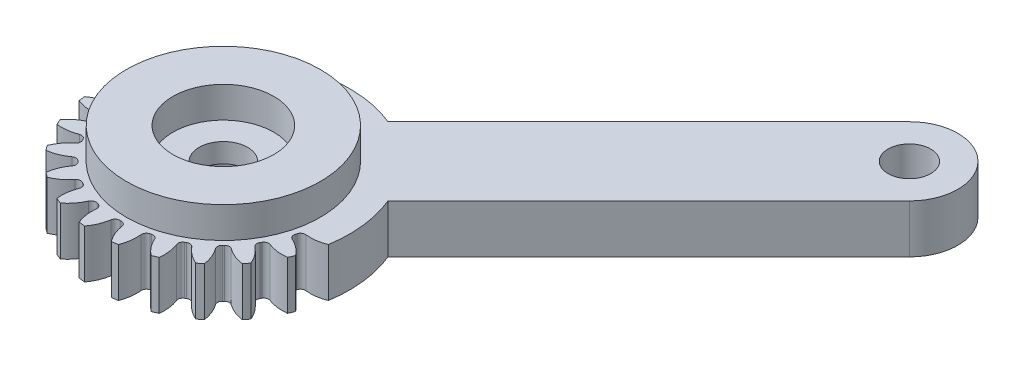
SolidWorks part; units mm, degrees
ref_plane "Front Plane" through (0, 0, 0) normal (0, 0, 1) x (1, 0, 0)
ref_plane "Top Plane" through (0, 0, 0) normal (0, 1, 0) x (1, 0, 0)
ref_plane "Right Plane" through (0, 0, 0) normal (1, 0, 0) x (0, 0, -1)
sketch "Sketch2" plane through (0, 0, 0) normal (0, 1, 0) x (1, 0, 0)
  circle A0 centre (0, 0) radius 13
  circle A1 centre (0, 0) radius 5.2
  dimension "D1" = 10.4
  dimension "D2" = 26
extrude "Boss-Extrude1" add sketch "Sketch2" along normal blind 5
sketch "Sketch3" plane through (0, 5, 0) normal (0, 1, 0) x (1, 0, 0)
  line L0 (0, 0) -> (0, 13) construction
  line L1 (-0.5275, 10.5869) -> (0, 0) construction
  line L2 (0, 9.6865) -> (14.5717, -30.349) construction
  arc A0 (0.5275, 10.5869) -> (-0.5275, 10.5869) centre (0, 0) ccw
  arc A1 (0.8347, 11.9709) -> (-0.8347, 11.9709) centre (0, 0) ccw construction
  arc A2 (1.3791, 12.9266) -> (-1.3791, 12.9266) centre (0, 0) ccw
  circle A3 centre (0, 0) radius 13 construction
  arc A5 (-1.3791, 12.9266) -> (-0.5275, 10.5869) centre (-4.7448, 10.3768) cw
  arc A6 (1.3791, 12.9266) -> (0.5275, 10.5869) centre (4.7448, 10.3768) ccw
  point P16 (-0.7769, 11.821)
  dimension "D1" = 24
  dimension "D2" = 2.4
  dimension "D3" = 20
  dimension "D4" = 1.6708
extrude "Cut-Extrude1" cut sketch "Sketch3" against normal through all
fillet "Fillet1" radius 0.5 2 edges at (0.5275, 2.5, -10.5869) (-0.5275, 2.5, -10.5869)
fillet "圆角1" [suppressed] radius 0.2
pattern_circular "CirPattern1" count 24 over 360 about axis through (0, 5, 0) along (0, -1, 0) of "Cut-Extrude1", "Fillet1", "圆角1" reverse direction yes
sketch "草图3" plane through (0, 5, 0) normal (0, 1, 0) x (1, 0, 0)
  circle A0 centre (0, 0) radius 12 construction
  dimension "D1" = 24
sketch "草图4" plane through (0, 5, 0) normal (0, 1, 0) x (1, 0, 0)
  line L0 (0, 0) -> (35.3553, 35.3553) construction
  line L1 (9.1924, 2.1213) -> (38.8909, 31.8198)
  line L2 (2.1213, 9.1924) -> (31.8198, 38.8909)
  line L3 (2.1213, 9.1924) -> (9.1924, 2.1213)
  line L5 (-5.2, 0) -> (5.2, 0) construction
  line L6 (-1.6968, 12.8888) -> (-1.2314, 9.3533)
  line L7 (9.3533, -1.2314) -> (12.8888, -1.6968)
  arc A0 (38.8909, 31.8198) -> (31.8198, 38.8909) centre (35.3553, 35.3553) ccw
  circle A1 centre (35.3553, 35.3553) radius 2.2
  circle A2 centre (0, 0) radius 5.2 construction
  arc A3 (4.9749, 12.0104) -> (-1.6968, 12.8888) centre (0, 0) ccw
  arc A4 (5.269, 11.8843) -> (4.6777, 12.1293) centre (0, 0) ccw construction
  arc A5 (-1.3791, 12.9266) -> (-2.0136, 12.8431) centre (0, 0) ccw construction
  arc A6 (2.1213, 9.1924) -> (-1.2314, 9.3533) centre (0, 0) ccw
  arc A7 (12.8888, -1.6968) -> (12.0208, 4.9497) centre (0, 0) ccw
  arc A9 (12.8431, -2.0136) -> (12.9266, -1.3791) centre (0, 0) ccw construction
  arc A10 (9.3533, -1.2314) -> (9.1924, 2.1213) centre (0, 0) ccw
  point P7 (5.6569, 5.6569)
  dimension "D3" = 4.4
  dimension "D1" = 50
  dimension "D2" = 8
  dimension "D4" = 10
  dimension "D5" = 45
extrude "凸台-拉伸1" add sketch "草图4" against normal up to surface (5 mm away) contours A6 L2 A3 L6 | L1 A0 L2 L3 A1 | A10 L7 A7 L1 region at (21.4435, 5, -21.4435) region at (11.2536, 5, -1.1324) region at (1.1324, 5, -11.2536) up to face at (0, 0, 5.2)
sketch "草图5" plane through (0, 5, 0) normal (0, 1, 0) x (1, 0, 0)
  circle A0 centre (0, 0) radius 10
  circle A1 centre (0, 0) radius 5.2 construction
  circle A2 centre (0, 0) radius 5.2
  dimension "D1" = 20
extrude "凸台-拉伸2" add sketch "草图5" along normal blind 3.2
sketch "草图6" plane through (0, 0, 0) normal (0, -1, 0) x (1, 0, 0)
  circle A0 centre (0, 0) radius 6
  dimension "D1" = 12
extrude "切除-拉伸1" cut sketch "草图6" against normal blind 3
sketch "草图7" plane through (0, 3, 0) normal (0, -1, 0) x (1, 0, 0)
  circle A0 centre (0, 0) radius 5.2
  circle A1 centre (0, 0) radius 2.5
  circle A2 centre (0, 0) radius 5.2 construction
  dimension "D1" = 5
extrude "凸台-拉伸3" add sketch "草图7" against normal blind 2
equation "\"No. of teeth\"= 24"
equation "\"Module\"= 1"
equation "\"Bore diameter\"= 10.4"
equation "\"Pressure angle\"= 20"
equation "\"Outer diameter\"= ( \"No. of teeth\" + 2 ) * \"Module\""
equation "\"Pitch diameter\"= \"No. of teeth\" * \"Module\""
equation "\"Backlash\"= 0.1"
equation "\"Arc length\"= ( ( \"Module\" * pi ) / 2 ) + \"Backlash\""
equation "\"Fillet radius\"= 0.5"
equation "\"Tooth depth\"= IIF ( \"Module\" <= 1.25 , \"Module\" * 2.4 , \"Module\" * 2.25 )"
equation "\"D1@Sketch2\"=\"Bore diameter\""
equation "\"D2@Sketch2\"=\"Outer diameter\""
equation "\"D1@Sketch3\"=\"Pitch diameter\""
equation "\"D2@Sketch3\"=\"Tooth depth\""
equation "\"D3@Sketch3\"=\"Pressure angle\""
equation "\"D4@Sketch3\"=\"Arc length\""
equation "\"D1@Fillet1\"=\"Fillet radius\""
equation "\"D1@CirPattern1\"=\"No. of teeth\""
equation "\"Gear thickness\"=5"
equation "\"D1@Boss-Extrude1\"=\"Gear thickness\""
